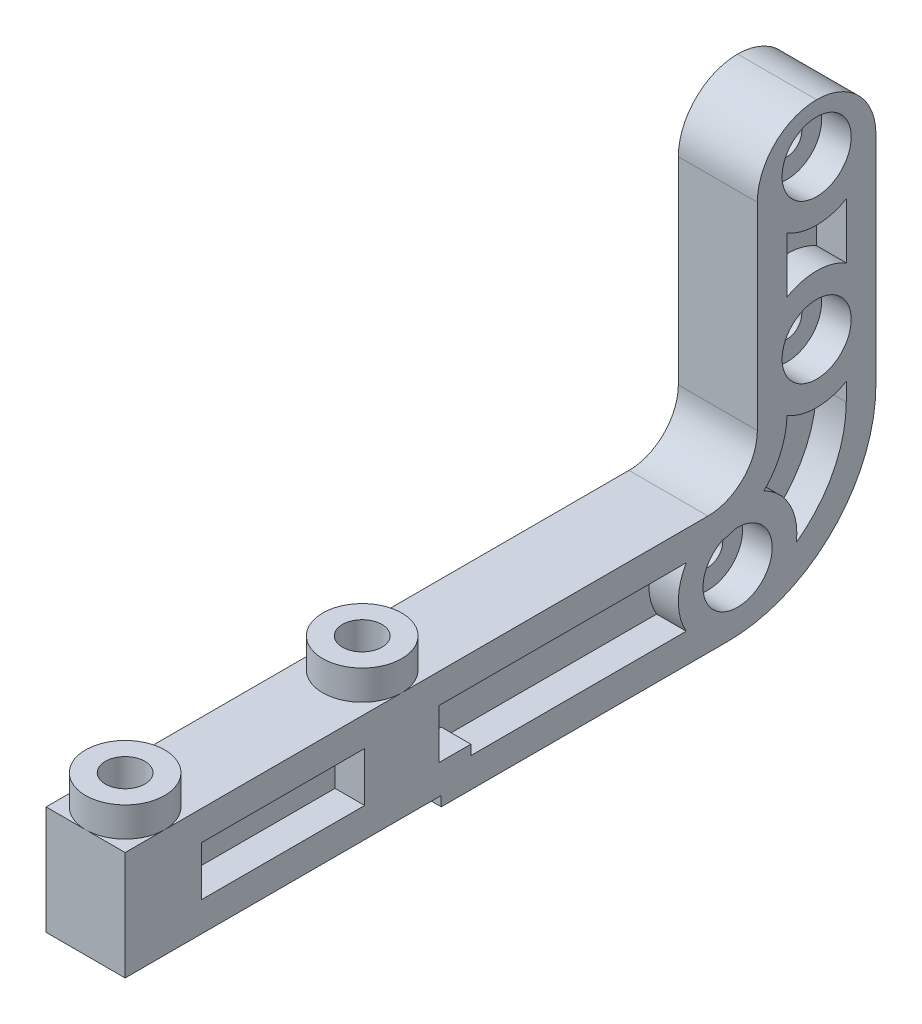
SolidWorks part; units mm, degrees
material "ABS"
ref_plane "Front Plane" through (0, 0, 0) normal (0, 0, 1) x (1, 0, 0)
ref_plane "Top Plane" through (0, 0, 0) normal (0, 1, 0) x (1, 0, 0)
ref_plane "Right Plane" through (0, 0, 0) normal (1, 0, 0) x (0, 0, -1)
sketch "Sketch1" plane through (0, 0, 0) normal (1, 0, 0) x (0, 0, -1)
  line L0 (32, 37) -> (32, 16) construction
  line L1 (-38, -6) -> (38, -6)
  line L2 (-38, -6) -> (-38, 6)
  line L3 (-38, 6) -> (38, 6)
  line L4 (38, -6) -> (38, 6)
  line L5 (-38, -6) -> (38, 6) construction
  line L6 (-38, 6) -> (38, -6) construction
  line L7 (38, 6) -> (26, 6)
  line L8 (38, 6) -> (38, 37)
  line L9 (38, 37) -> (26, 37)
  line L10 (26, 6) -> (26, 37)
  line L11 (-38, -6) -> (-6, -6)
  line L12 (-38, -6) -> (-38, -5)
  line L13 (-38, -5) -> (-6, -5)
  line L14 (-6, -6) -> (-6, -5)
  circle A0 centre (32, 32) radius 1.5
  circle A1 centre (32, 16) radius 1.5
  circle A2 centre (24, 0) radius 1.5
  point P0 (0, 0)
  dimension "D7" = 3
  dimension "D8" = 3
  dimension "D9" = 3
  dimension "D10" = 16
  dimension "D11" = 5
  dimension "D12" = 8
  dimension "D13" = 6
  dimension "D14" = 6
  dimension "D1" = 12
  dimension "D2" = 12
  dimension "D3" = 76
  dimension "D4" = 43
  dimension "D5" = 1
  dimension "D6" = 32
extrude "Boss-Extrude1" add sketch "Sketch1" along normal blind 8 contours L14 L1 L4 L3 L2 L13 A2 | L10 L3 L8 L9 A1 A0 region at (0, 0.2016, -0.6121) region at (0, 21.4012, -32)
fillet "Fillet1" radius 6 2 edges at (4, 37, -26) (4, 37, -38)
fillet "Fillet2" radius 15 1 edges at (4, -6, -38)
fillet "Fillet3" radius 5 1 edges at (4, 6, -26)
sketch "Sketch2" plane through (0, 6, 0) normal (0, 1, 0) x (1, 0, 0)
  line L0 (4, -10) -> (4, -34) construction
  line L1 (4, -34) -> (4, -38) construction
  line L2 (8, -38) -> (0, -38) construction
  circle A0 centre (4, -34) radius 2
  circle A1 centre (4, -10) radius 2
  dimension "D1" = 4
  dimension "D2" = 4
  dimension "D3" = 4
  dimension "D4" = 24
extrude "Cut-Extrude1" cut sketch "Sketch2" against normal through all
sketch "Sketch3" plane through (0, 6, 0) normal (0, 1, 0) x (1, 0, 0)
  circle A0 centre (4, -10) radius 4
  circle A1 centre (4, -34) radius 4
  circle A4 centre (4, -10) radius 2
  circle A5 centre (4, -10) radius 2
  circle A7 centre (4, -34) radius 2
  circle A8 centre (4, -34) radius 2
  dimension "D1" = 8
  dimension "D2" = 8
  dimension "D3" = 0
  dimension "D4" = 0
extrude "Boss-Extrude2" add sketch "Sketch3" along normal blind 3
sketch "Sketch4" plane through (8, 0, 0) normal (1, 0, 0) x (0, 0, -1)
  line L9 (-6, 6) -> (-6, 9) construction
  line L10 (-13.75, -2) -> (-6.25, -2)
  line L11 (-13.75, -2) -> (-13.75, 3)
  line L12 (-13.75, 3) -> (-6.25, 3)
  line L13 (-6.25, -2) -> (-6.25, 3)
  line L14 (-13.75, -2) -> (-6.25, 3) construction
  line L15 (-13.75, 3) -> (-6.25, -2) construction
  line L16 (-30.25, 3) -> (-35, 3)
  line L17 (-30.25, 3) -> (-30.25, -2)
  line L18 (-3, -3) -> (23, -3)
  line L19 (35, 9) -> (35, 31)
  line L20 (29, 31) -> (29, 11)
  line L21 (21, 3) -> (-10, 3)
  line L22 (-10, 3) -> (-34, 3)
  line L23 (-34, 3) -> (-35, 3)
  line L24 (-35, 3) -> (-35, -2)
  line L25 (-35, -2) -> (-3, -2)
  line L26 (-3, -2) -> (-3, -3)
  line L27 (-3, -3) -> (23, -3)
  line L28 (35, 9) -> (35, 31)
  line L29 (29, 31) -> (29, 11)
  line L30 (21, 3) -> (-10, 3)
  line L31 (-10, 3) -> (-34, 3)
  line L32 (-34, 3) -> (-35, 3)
  line L33 (-35, 3) -> (-35, -2)
  line L34 (-35, -2) -> (-3, -2)
  line L35 (-3, -2) -> (-3, -3)
  line L36 (-30.25, -2) -> (-35, -2)
  line L37 (-35, 3) -> (-35, -2)
  circle A0 centre (32, 32) radius 3.5
  circle A1 centre (32, 16) radius 3.5
  circle A2 centre (24, 0) radius 3.5
  circle A7 centre (24, 0) radius 6
  circle A8 centre (32, 16) radius 6
  circle A9 centre (32, 32) radius 6
  arc A11 (23, -3) -> (35, 9) centre (23, 9) ccw
  arc A12 (35, 31) -> (32, 34) centre (32, 31) ccw
  arc A13 (32, 34) -> (29, 31) centre (32, 31) ccw
  arc A14 (21, 3) -> (29, 11) centre (21, 11) ccw
  arc A15 (23, -3) -> (35, 9) centre (23, 9) ccw
  arc A16 (35, 31) -> (32, 34) centre (32, 31) ccw
  arc A17 (32, 34) -> (29, 31) centre (32, 31) ccw
  arc A18 (21, 3) -> (29, 11) centre (21, 11) ccw
  point P9 (-10, 0.5)
  circle M18 centre (24, 0) radius 1.5
  circle M32 centre (32, 16) radius 1.5
  circle M33 centre (32, 32) radius 1.5
  dimension "D1" = 7
  dimension "D2" = 7
  dimension "D3" = 7
  dimension "D9" = 12
  dimension "D10" = 12
  dimension "D11" = 12
  dimension "D5" = 3.75
  dimension "D6" = 7.5
  dimension "D7" = 4
  dimension "D8" = 0
  dimension "D4" = 3
extrude "Cut-Extrude2" cut sketch "Sketch4" against normal blind 3 contours A7 L30 L13 L34 L35 L27 | L17 L34 L11 L31 | A18 A7 A15 L28 A8 | A9 L29 A8 L28 | A16 A17 L29 A0 L28 M33 | A17 A16 L28 A0 L29 | L28 A1 L29 M32 | L28 A1 | L29 A1 | A18 A2 L27 A15 M18 | A15 L27 A2 region at (8, 0.5, 22) region at (8, 0.0565, -6.2466) region at (8, 5.9721, -31.3123) region at (8, 3.1897, -23.1301) region at (8, -3.1103, -24.3549) region at (8, 24, -32) region at (8, 19.4078, -32) region at (8, 16, -28.7987) region at (8, 16, -35.2013) region at (8, 35.2881, -31.0881) region at (8, 30.5986, -29.0814)
ref_plane "Plane1" through (4, 0, 0) normal (-1, 0, 0) x (0, 0, 1)
mirror "Mirror1" about plane through (4, 0, 0) normal (-1, 0, 0) of "Cut-Extrude2"
